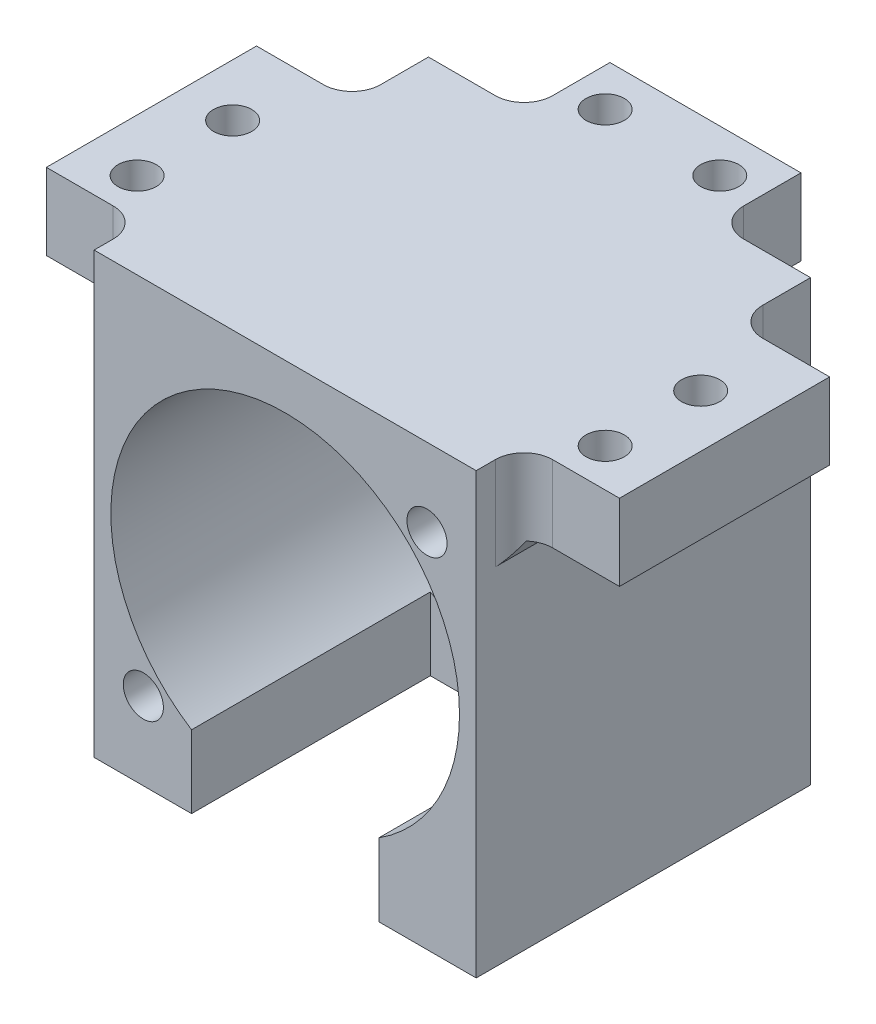
SolidWorks part; units mm, degrees
material "6061 合金"
ref_plane "前视基准面" through (0, 0, 0) normal (0, 0, 1) x (1, 0, 0)
ref_plane "上视基准面" through (0, 0, 0) normal (0, 1, 0) x (1, 0, 0)
ref_plane "右视基准面" through (0, 0, 0) normal (1, 0, 0) x (0, 0, -1)
sketch "草图1" plane through (0, 0, 0) normal (0, 0, 1) x (1, 0, 0)
  line L1 (-23, 23) -> (23, 23)
  line L2 (-23, 23) -> (-23, -23)
  line L3 (-23, -23) -> (23, -23)
  line L4 (23, 23) -> (23, -23)
  line L5 (-23, 23) -> (23, -23) construction
  line L6 (-23, -23) -> (23, 23) construction
  point P0 (0, 0)
  dimension "D1" = 46
extrude "凸台-拉伸1" add sketch "草图1" along normal blind 35
sketch "草图2" plane through (0, 0, 35) normal (0, 0, 1) x (1, 0, 0)
  circle A0 centre (0, 0) radius 3
  dimension "D1" = 6
sketch "草图3" plane through (0, 0, 35) normal (0, 0, 1) x (1, 0, 0)
  circle A0 centre (0, 0) radius 18.25
  dimension "D1" = 36.5
extrude "切除-拉伸1" cut sketch "草图3" against normal blind 29
sketch "草图4" plane through (0, 0, 35) normal (0, 0, 1) x (1, 0, 0)
  line L0 (-8.8, -15.1265) -> (-8.8, -23.08)
  line L1 (-8.8, -23.08) -> (8.8, -23.08)
  line L2 (8.8, -23.08) -> (8.8, -15.1265)
  line L3 (-9.8, -15.3955) -> (-9.8, -24.08)
  line L4 (-9.8, -24.08) -> (9.8, -24.08)
  line L5 (9.8, -24.08) -> (9.8, -15.3955)
  line L6 (-9.8, -15.1265) -> (-9.8, -24.08) construction
  line L7 (9.8, -24.08) -> (9.8, -15.1265) construction
  circle A0 centre (0, 0) radius 18.25 construction
  circle A1 centre (0, 0) radius 17.5
  circle M2 centre (0, 0) radius 18.25
  line M6 (-23, -23) -> (23, -23)
  dimension "D1" = 1
extrude "切除-拉伸2" cut sketch "草图4" against normal blind 25 contours L2 L0 M6 M2 | L3 L0 M2 M6 | L4 L5 L2 L1 L0 L3 M6 | L5 L2 M6 M2 region at (0, -20.2173, 35) region at (-9.3068, -19.3475, 35) region at (0, -23.5756, 35) region at (9.3068, -19.3475, 35)
sketch "草图5" plane through (0, 0, 35) normal (0, 0, 1) x (1, 0, 0)
  circle A0 centre (-14.8492, -14.8492) radius 2.1
  circle A1 centre (14.8492, 14.8492) radius 2.1
extrude "切除-拉伸3" cut sketch "草图5" against normal through all
sketch "草图6" plane through (0, 0, 0) normal (0, 0, -1) x (-1, 0, 0)
  line L1 (-10.8655, 14.8492) -> (-12.8574, 18.2992)
  line L2 (-12.8574, 18.2992) -> (-16.8411, 18.2992)
  line L3 (-16.8411, 18.2992) -> (-18.833, 14.8492)
  line L4 (-18.833, 14.8492) -> (-16.8411, 11.3992)
  line L5 (-16.8411, 11.3992) -> (-12.8574, 11.3992)
  line L6 (-12.8574, 11.3992) -> (-10.8655, 14.8492)
  line L7 (18.833, -14.8492) -> (16.8411, -11.3992)
  line L8 (16.8411, -11.3992) -> (12.8574, -11.3992)
  line L9 (12.8574, -11.3992) -> (10.8655, -14.8492)
  line L10 (10.8655, -14.8492) -> (12.8574, -18.2992)
  line L11 (12.8574, -18.2992) -> (16.8411, -18.2992)
  line L12 (16.8411, -18.2992) -> (18.833, -14.8492)
  circle A0 centre (-14.8492, 14.8492) radius 3.45 construction
  circle A1 centre (14.8492, -14.8492) radius 3.45 construction
  dimension "D1" = 6.9
  dimension "D2" = 6.9
extrude "切除-拉伸4" cut sketch "草图6" against normal blind 5
sketch "草图7" plane through (0, -23, 0) normal (0, -1, 0) x (1, 0, 0)
  line L0 (-23, 0) -> (23, 0) construction
  line L1 (23, 35) -> (20, 35)
  line L2 (23, 35) -> (23, 0)
  line L3 (23, 0) -> (20, 0)
  line L4 (20, 35) -> (20, 0)
  line L6 (-23, 0) -> (-20, 0)
  line L7 (-23, 0) -> (-23, 35.0254)
  line L8 (-23, 35.0254) -> (-20, 35.0254)
  line L9 (-20, 0) -> (-20, 35.0254)
  dimension "D1" = 3
  dimension "D2" = 3
extrude "切除-拉伸5" cut sketch "草图7" against normal blind 61
sketch "草图8" plane through (0, 23, 0) normal (0, 1, 0) x (1, 0, 0)
  line L0 (20, -35) -> (20, 0) construction
  line L1 (20, -30) -> (30, -30)
  line L2 (20, -30) -> (20, -8)
  line L3 (20, -8) -> (30, -8)
  line L4 (30, -30) -> (30, -8)
  line L5 (9.8, -35) -> (20, -35) construction
  line L6 (0, 0) -> (0, -41.4363) construction
  line L7 (-20, -8) -> (-30, -8)
  line L8 (-30, -30) -> (-30, -8)
  line L9 (-20, -30) -> (-30, -30)
  line L10 (-20, -30) -> (-20, -8)
  line L11 (20, 0) -> (-20, 0) construction
  line L12 (-10, 0) -> (10, 0)
  line L13 (-10, 0) -> (-10, 9)
  line L14 (-10, 9) -> (10, 9)
  line L15 (10, 0) -> (10, 9)
  line L16 (0, 0) -> (0, 9) construction
  line L17 (10, 4.5) -> (-10, 4.5) construction
  circle A0 centre (6, 4.5) radius 2
  circle A1 centre (-6, 4.5) radius 2
  dimension "D6" = 4
  dimension "D7" = 12
  dimension "D1" = 22
  dimension "D2" = 10
  dimension "D3" = 5
  dimension "D4" = 20
  dimension "D5" = 9
extrude "凸台-拉伸2" add sketch "草图8" against normal blind 8
sketch "草图9" plane through (0, 15, 0) normal (0, -1, 0) x (1, 0, 0)
  line L0 (0, 0) -> (0, 43.4924) construction
  line L1 (24.5, 26) -> (24.5, 16) construction
  line L2 (9.8, 35) -> (20, 35) construction
  circle A0 centre (24.5, 26) radius 2
  circle A1 centre (24.5, 16) radius 2
  circle A2 centre (-24.5, 16) radius 2
  circle A3 centre (-24.5, 26) radius 2
  dimension "D1" = 4
  dimension "D3" = 4
  dimension "D2" = 10
  dimension "D4" = 9
  dimension "D5" = 49
extrude "切除-拉伸6" cut sketch "草图9" against normal through all
chamfer "倒角1" distance 1 angle 60 3 edges at (0, 15, 0) (20, 15, 19) (-20, 15, 19) first distance on face at (-6, 15, -2.5) first distance on face at (24.5, 15, 14) first distance on face at (-24.5, 15, 28)
fillet "圆角2" radius 3 6 edges at (-20, 18.134, 30) (-20, 18.134, 8) (-10, 18.134, 0) (10, 18.134, 0) (20, 18.134, 8) (20, 18.134, 30)
